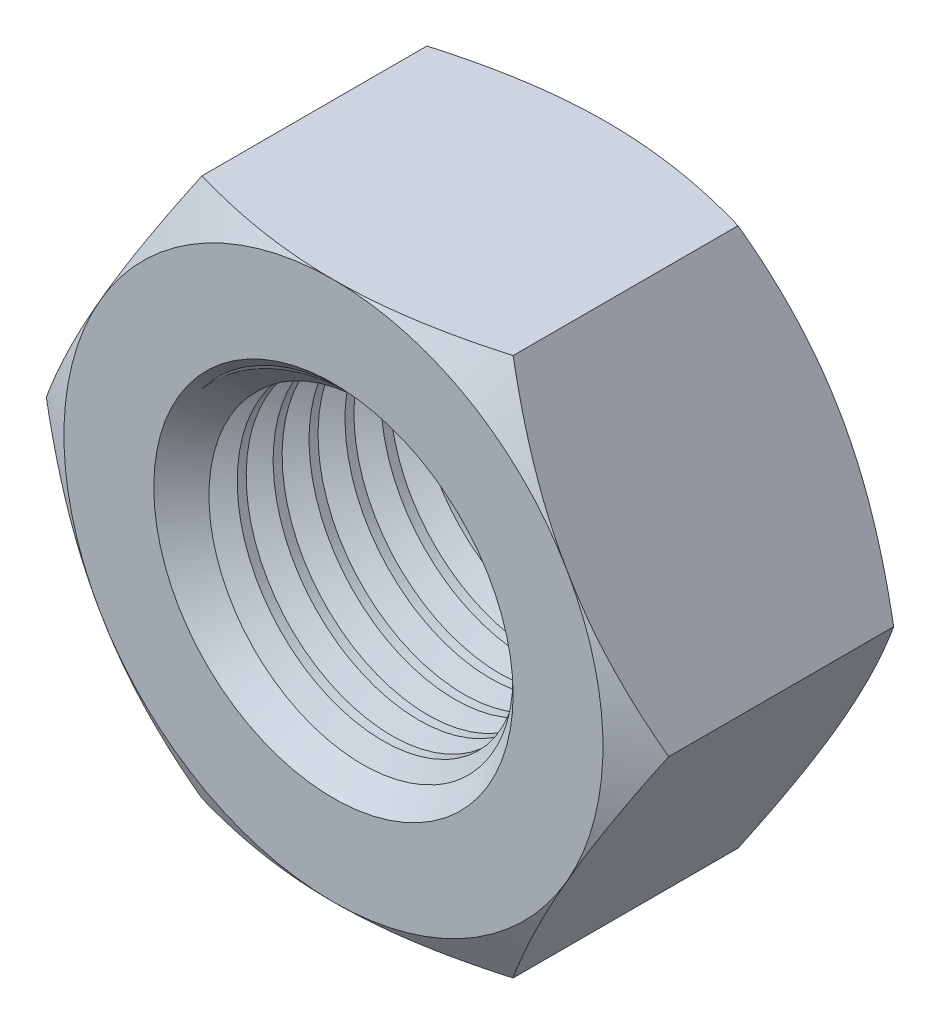
SolidWorks part; units mm, degrees
ref_plane "Front" through (0, 0, 0) normal (0, 0, 1) x (1, 0, 0)
ref_plane "Top" through (0, 0, 0) normal (0, 1, 0) x (1, 0, 0)
ref_plane "Right" through (0, 0, 0) normal (1, 0, 0) x (0, 0, -1)
sketch "Çizim1" plane through (0, 0, 0) normal (0, 0, 1) x (1, 0, 0)
  line L1 (43.3013, 0) -> (21.6506, 37.5)
  line L2 (21.6506, 37.5) -> (-21.6506, 37.5)
  line L3 (-21.6506, 37.5) -> (-43.3013, 0)
  line L4 (-43.3013, 0) -> (-21.6506, -37.5)
  line L5 (-21.6506, -37.5) -> (21.6506, -37.5)
  line L6 (21.6506, -37.5) -> (43.3013, 0)
  circle A0 centre (0, 0) radius 37.5 construction
  point P1 (0, 0)
  dimension "D1" = 75
extrude "Yükseklik-Ekstrüzyon1" add sketch "Çizim1" along normal blind 38
sketch "Çizim2" plane through (0, 0, 38) normal (0, 0, 1) x (1, 0, 0)
  circle A0 centre (0, 0) radius 37.5
extrude "Kes-Ekstrüzyon1" cut sketch "Çizim2" against normal blind 38 draft 60 flip side to cut
sketch "Çizim3" plane through (0, 0, 0) normal (0, 0, -1) x (-1, 0, 0)
  circle A0 centre (0, 0) radius 37.5
extrude "Kes-Ekstrüzyon2" cut sketch "Çizim3" against normal blind 38 draft 60 flip side to cut
sketch "Çizim4" plane through (0, 0, 38) normal (0, 0, 1) x (1, 0, 0)
  circle A0 centre (0, 0) radius 20.75
  dimension "D1" = 41.5
extrude "Kes-Ekstrüzyon3" cut sketch "Çizim4" against normal blind 38
chamfer "Pah1" distance 4.25 angle 45 2 edges at (20.75, 0, 0) (20.75, 0, 38)
sketch "Çizim5" plane through (0, 0, 0) normal (0, 0, -1) x (-1, 0, 0)
  circle A0 centre (0, 0) radius 20.75
curve "Helis/Spiral1" pitch 5 height 45 radius 20.75 centre (0, 0, 0) axis (0, 0, 1) start towards (1, 0, 0)
ref_plane "Düzlem1" through (20.75, 0, 45) normal (0, 0.9993, 0.0383) x (1, 0, 0)
sketch "Çizim6" plane through (20.75, 0, 45) normal (0, 0.9993, 0.0383) x (1, 0, 0)
  line L1 (3.25, 0) -> (-1.0018, 2.4548)
  line L3 (-1.0018, -2.4548) -> (3.25, 0)
  line L4 (-1.0018, 2.4548) -> (-1.0018, -2.4548)
  line L5 (-1.625, 2.8146) -> (-1.625, 0) [skipped]
  circle A0 centre (0, 0) radius 1.625 construction
  dimension "D1" = 3.25
sweep "Kes-Süpür1" cut profiles "Çizim6" path "Helis/Spiral1" align with end faces yes
